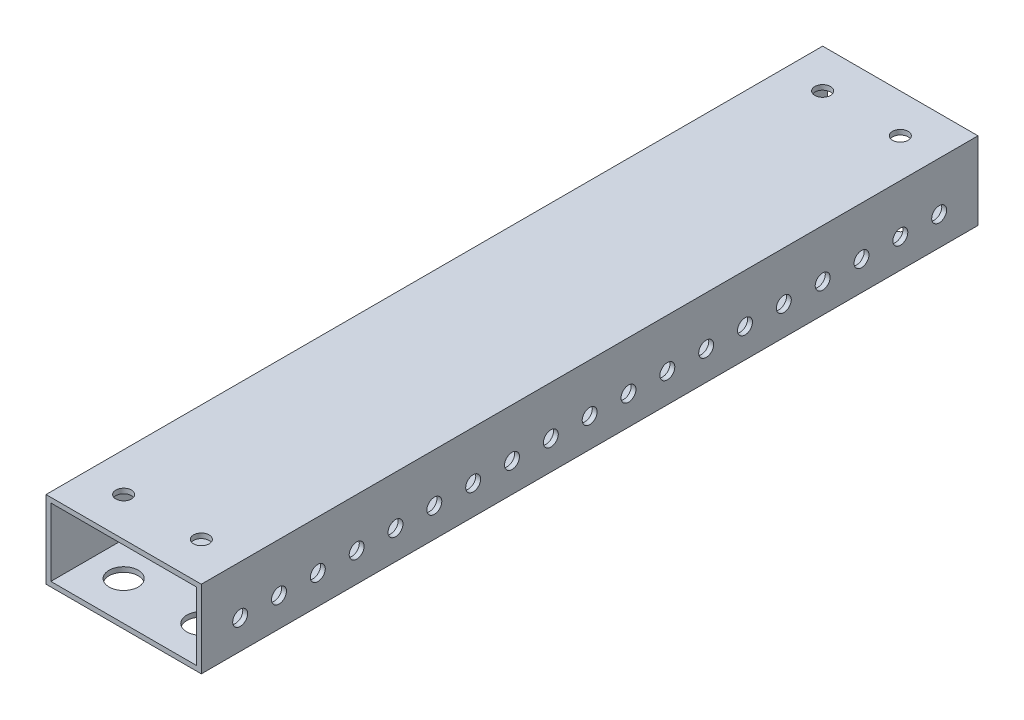
SolidWorks part; units mm, degrees
other "Markup1"
sketch "Sketch7" plane through (25.4, 12.7, -127) normal (0.9965, 0.0171, -0.0817) x (-0.082, 0.0128, -0.9966)
sketch "Sketch8" plane through (25.4, 12.7, -127) normal (0.9965, 0.0171, -0.0817) x (-0.082, 0.0128, -0.9966)
material "6061-T6 (SS)"
ref_plane "Front Plane" through (0, 0, 0) normal (0, 0, 1) x (1, 0, 0)
ref_plane "Top Plane" through (0, 0, 0) normal (0, 1, 0) x (1, 0, 0)
ref_plane "Right Plane" through (0, 0, 0) normal (1, 0, 0) x (0, 0, -1)
sketch "Sketch1" plane through (0, 0, 0) normal (0, 0, 1) x (1, 0, 0)
  line L0 (-23.8125, 11.1125) -> (23.8125, 11.1125)
  line L1 (-25.4, -12.7) -> (25.4, -12.7)
  line L2 (-25.4, -12.7) -> (-25.4, 12.7)
  line L3 (-25.4, 12.7) -> (25.4, 12.7)
  line L4 (25.4, -12.7) -> (25.4, 12.7)
  line L5 (-25.4, -12.7) -> (25.4, 12.7) construction
  line L6 (-25.4, 12.7) -> (25.4, -12.7) construction
  line L7 (23.8125, -11.1125) -> (23.8125, 11.1125)
  line L8 (-23.8125, -11.1125) -> (23.8125, -11.1125)
  line L9 (-23.8125, -11.1125) -> (-23.8125, 11.1125)
  point P0 (0, 0)
  dimension "D1" = 50.8
  dimension "D2" = 25.4
  dimension "D3" = 1.5875
extrude "Boss-Extrude1" add sketch "Sketch1" along normal mid plane 254
sketch "Sketch3" plane through (0, 12.7, 0) normal (0, 1, 0) x (1, 0, 0)
  line L0 (25.4, 127) -> (-25.4, 127) construction
  line L1 (25.4, -127) -> (-25.4, -127) construction
  line L3 (-25.4, -127) -> (-25.4, 127) construction
  line L4 (25.4, -127) -> (25.4, 127) construction
  circle A0 centre (-12.7, -114.3) radius 2.5527
  circle A1 centre (12.7, -114.3) radius 2.5527
  circle A2 centre (-12.7, 114.3) radius 2.5527
  circle A3 centre (12.7, 114.3) radius 2.5527
  dimension "D5" = 5.1054
  dimension "D1" = 12.7
  dimension "D2" = 12.7
  dimension "D3" = 12.7
  dimension "D4" = 12.7
  dimension "D6" = 25.4
  dimension "D7" = 25.4
  dimension "D8" = 12.7
  dimension "D9" = 12.7
  dimension "D10" = 12.7
  dimension "D11" = 12.7
extrude "Cut-Extrude1" cut sketch "Sketch3" against normal up to surface (1.5875 mm away) up to face at (0, 11.1125, 0)
sketch "Sketch5" plane through (0, -12.7, 0) normal (0, -1, 0) x (1, 0, 0)
  circle A0 centre (-12.7, -114.3) radius 2.5527 construction
  circle A1 centre (12.7, -114.3) radius 2.5527 construction
  circle A2 centre (12.7, 114.3) radius 2.5527 construction
  circle A3 centre (-12.7, 114.3) radius 2.5527 construction
  circle A4 centre (-12.7, -114.3) radius 2.5527
  circle A5 centre (12.7, -114.3) radius 2.5527
  circle A6 centre (12.7, 114.3) radius 2.5527
  circle A7 centre (-12.7, 114.3) radius 2.5527
  circle A8 centre (-12.7, 114.3) radius 4.7625
  circle A9 centre (12.7, 114.3) radius 4.7625
  circle A10 centre (12.7, -114.3) radius 4.7625
  circle A11 centre (-12.7, -114.3) radius 4.7625
  dimension "D1" = 9.525
extrude "Cut-Extrude2" cut sketch "Sketch5" against normal up to surface (1.5875 mm away) contours A10 A5 | A5 | A11 A4 | A4 | A6 | A9 A6 | A8 A7 | A7 region at (-12.7, -12.7, -114.3) region at (12.7, -12.7, -114.3) region at (12.7, -12.7, 114.3) region at (-12.7, -12.7, 114.3) region at (-17.3278, -12.7, 114.3) region at (8.0722, -12.7, 114.3) region at (8.0722, -12.7, -114.3) region at (-17.3278, -12.7, -114.3) up to face at (0, -11.1125, 0)
sketch "Sketch6" plane through (25.4, 0, 0) normal (1, 0, 0) x (0, 0, -1)
  line L0 (-127, -12.7) -> (-127, 12.7) construction
  line L1 (-127, -12.7) -> (127, -12.7) construction
  line L2 (0, 12.7) -> (0, -12.7) construction
  line L3 (-127, 12.7) -> (127, 12.7) construction
  circle A0 centre (-114.3, -3.175) radius 2.4384
  circle A1 centre (-101.6, -3.175) radius 2.4384
  circle A2 centre (-88.9, -3.175) radius 2.4384
  circle A3 centre (88.9, -3.175) radius 2.4384
  circle A4 centre (101.6, -3.175) radius 2.4384
  circle A5 centre (114.3, -3.175) radius 2.4384
  circle A6 centre (-76.2, -3.175) radius 2.4384
  circle A7 centre (-63.5, -3.175) radius 2.4384
  circle A8 centre (-50.8, -3.175) radius 2.4384
  circle A9 centre (-38.1, -3.175) radius 2.4384
  circle A10 centre (-25.4, -3.175) radius 2.4384
  circle A11 centre (-12.7, -3.175) radius 2.4384
  circle A12 centre (0, -3.175) radius 2.4384
  circle A13 centre (12.7, -3.175) radius 2.4384
  circle A14 centre (25.4, -3.175) radius 2.4384
  circle A15 centre (38.1, -3.175) radius 2.4384
  circle A16 centre (50.8, -3.175) radius 2.4384
  circle A17 centre (63.5, -3.175) radius 2.4384
  circle A18 centre (76.2, -3.175) radius 2.4384
  dimension "D1" = 4.8768
  dimension "D7" = 4.8768
  dimension "D2" = 12.7
  dimension "D3" = 9.525
  dimension "D4" = 12.7
  dimension "D5" = 12.7
  dimension "D6" = 12.7
  dimension "D8" = 9.525
  dimension "D10" = 12.7
  dimension "D9" = 13
extrude "Cut-Extrude3" cut sketch "Sketch6" against normal up to surface (1.5875 mm away) contours A5 | A4 | A3 | A0 | A1 | A2 | A6 | A7 | A8 | A9 | A10 | A11 | A12 L2 | L2 A12 | A13 | A14 | A15 | A16 | A17 | A18 | A12 region at (25.4, -3.175, -1.0349) region at (25.4, -3.175, 1.0349) region at (25.4, -3.175, 114.3) region at (25.4, -3.175, 101.6) region at (25.4, -3.175, 88.9) region at (25.4, -3.175, -88.9) region at (25.4, -3.175, -101.6) region at (25.4, -3.175, -114.3) region at (25.4, -3.175, 76.2) region at (25.4, -3.175, 63.5) region at (25.4, -3.175, 50.8) region at (25.4, -3.175, 38.1) region at (25.4, -3.175, 25.4) region at (25.4, -3.175, 12.7) region at (25.4, -3.175, -12.7) region at (25.4, -3.175, -25.4) region at (25.4, -3.175, -38.1) region at (25.4, -3.175, -50.8) region at (25.4, -3.175, -63.5) region at (25.4, -3.175, -76.2) up to face at (23.8125, 0, 0)
